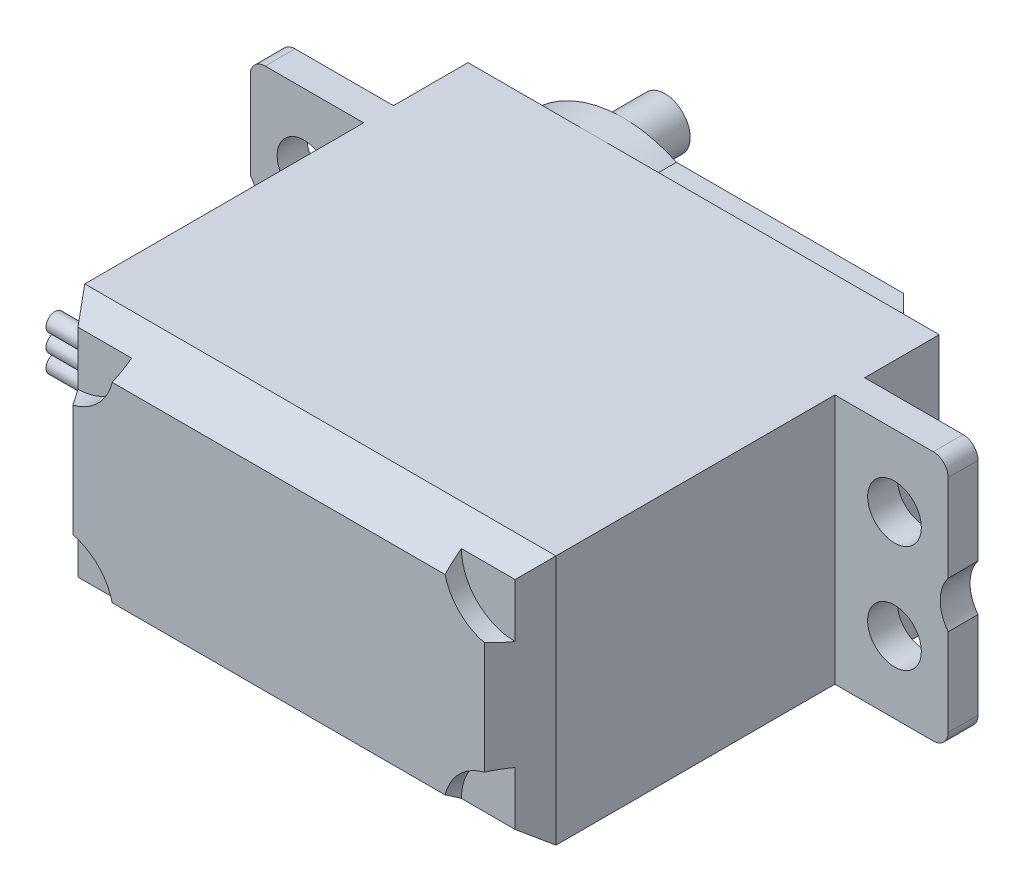
SolidWorks part; units mm, degrees
ref_plane "Front Plane" through (0, 0, 0) normal (0, 0, 1) x (1, 0, 0)
ref_plane "Top Plane" through (0, 0, 0) normal (0, 1, 0) x (1, 0, 0)
ref_plane "Right Plane" through (0, 0, 0) normal (1, 0, 0) x (0, 0, -1)
sketch "Sketch1" plane through (0, 0, 0) normal (0, 0, 1) x (1, 0, 0)
  line L1 (-22.8104, 16.0029) -> (17.3216, 16.0029)
  line L2 (-22.8104, 16.0029) -> (-22.8104, -5.3331)
  line L3 (-22.8104, -5.3331) -> (17.3216, -5.3331)
  line L4 (17.3216, 16.0029) -> (17.3216, -5.3331)
  dimension "D1" = 40.132
  dimension "D2" = 21.336
extrude "Boss-Extrude1" add sketch "Sketch1" along normal blind 36.195
sketch "Sketch5" plane through (0, -5.3331, 0) normal (0, -1, 0) x (1, 0, 0)
  line L0 (-22.8104, 36.195) -> (17.3216, 36.195) construction
  line L1 (-22.8104, 36.195) -> (-22.8104, 0) construction
  line L2 (-22.8104, 0) -> (17.3216, 0) construction
  line L3 (17.3216, 36.195) -> (17.3216, 0) construction
  line L4 (-22.8104, 36.195) -> (17.3216, 36.195)
  line L5 (-22.8104, 36.195) -> (-22.8104, 0)
  line L6 (-22.8104, 0) -> (17.3216, 0)
  line L7 (17.3216, 36.195) -> (17.3216, 0)
sketch "Sketch6" plane through (0, 0, 0) normal (0, 0, -1) x (-1, 0, 0)
  line L0 (22.8104, 16.0029) -> (22.8104, -5.3331) construction
  line L1 (7.5987, 14.9869) -> (-14.2736, 14.9869)
  line L2 (22.8104, -5.3331) -> (-17.3216, -5.3331) construction
  line L3 (-17.3216, 16.0029) -> (22.8104, 16.0029) construction
  line L4 (-14.2736, 14.9869) -> (-14.2736, -4.3171)
  line L5 (-14.2736, -4.3171) -> (7.5987, -4.3171)
  line L6 (22.8104, -5.3331) -> (-17.3216, -5.3331) construction
  line L7 (-17.3216, -5.3331) -> (-17.3216, 16.0029) construction
  circle A0 centre (12.1424, 5.3349) radius 10.668 construction
  arc A1 (7.5987, -4.3171) -> (7.5987, 14.9869) centre (12.1424, 5.3349) ccw
  point P6 (22.8104, 5.3349)
  dimension "D1" = 1.016
  dimension "D2" = 1.016
  dimension "D3" = 3.048
extrude "Boss-Extrude3" add sketch "Sketch6" along normal blind 2.54
chamfer "Chamfer1" distance 2.54 distance2 2.54 1 edges at (14.2736, 5.3349, -2.54)
ref_plane "Plane1" through (0, 0, 8.89) normal (0, 0, -1) x (-1, 0, 0)
sketch "Sketch7" plane through (0, 0, 8.89) normal (0, 0, -1) x (-1, 0, 0)
  line L0 (22.8104, 16.0029) -> (22.8104, -5.3331) construction
  line L1 (22.8104, 16.0029) -> (22.8104, -5.3331)
  line L2 (22.8104, -5.3331) -> (31.1924, -5.3331)
  line L3 (32.4624, -4.0631) -> (32.4624, 3.3593)
  line L4 (31.1924, 16.0029) -> (22.8104, 16.0029)
  line L5 (32.4624, 5.3349) -> (22.8104, 5.3349) construction
  line L6 (32.4624, 5.3349) -> (35.0024, 5.3349) construction
  line L7 (32.4624, 7.3105) -> (32.4624, 14.7329)
  circle A0 centre (27.8904, 0.7629) radius 2.286
  circle A1 centre (27.8904, 9.9069) radius 2.286
  arc A2 (32.4624, 3.3593) -> (32.4624, 7.3105) centre (35.0024, 5.3349) cw
  arc A3 (32.4624, 14.7329) -> (31.1924, 16.0029) centre (31.1924, 14.7329) ccw
  arc A4 (31.1924, -5.3331) -> (32.4624, -4.0631) centre (31.1924, -4.0631) ccw
  point P17 (32.4624, -5.3331)
  dimension "D2" = 4.572
  dimension "D3" = 4.572
  dimension "D9" = 2.54
  dimension "D10" = 1.27
  dimension "D1" = 9.652
  dimension "D4" = 4.572
  dimension "D5" = 5.08
  dimension "D6" = 5.08
  dimension "D7" = 9.144
  dimension "D8" = 3.9511
extrude "Boss-Extrude4" add sketch "Sketch7" along normal blind 2.54
ref_plane "Plane2" through (-2.7444, 0, 0) normal (1, 0, 0) x (0, 0, -1)
mirror "Mirror1" about plane through (-2.7444, 0, 0) normal (1, 0, 0) of "Boss-Extrude4"
chamfer "Chamfer2" distance 3.556 distance2 2.54 4 edges at (17.3216, 5.3349, 36.195) (-2.7444, 16.0029, 36.195) (-2.7444, -5.3331, 36.195) (-22.8104, 5.3349, 36.195) first distance on face at (17.3216, 8.0019, 29.3687) first distance on face at (-2.8225, 16.0029, 11.5521) first distance on face at (-4.1121, -5.3331, 11.5521) first distance on face at (-22.8104, 5.3349, 22.5425)
ref_plane "Plane3" through (0, 0, 34.671) normal (0, 0, 1) x (1, 0, 0)
sketch "Sketch12" plane through (0, 0, 34.671) normal (0, 0, 1) x (1, 0, 0)
  line L0 (-21.3589, 14.5515) -> (-21.3589, -3.8817)
  line L1 (-21.3589, 14.5515) -> (-21.3589, 9.9795)
  line L2 (15.8702, 14.5515) -> (-21.3589, 14.5515)
  line L3 (15.8702, 14.5515) -> (11.2982, 14.5515)
  line L4 (15.8702, -3.8817) -> (15.8702, 14.5515)
  line L5 (15.8702, -3.8817) -> (15.8702, 0.6903)
  line L6 (-21.3589, -3.8817) -> (15.8702, -3.8817)
  line L7 (-21.3589, -3.8817) -> (-16.7869, -3.8817)
  line L8 (-2.7444, 14.9143) -> (-2.7444, -4.2445) construction
  line L9 (-21.7218, 5.3349) -> (16.2331, 5.3349) construction
  line L10 (-21.3589, 0.6903) -> (-21.3589, -3.8817)
  line L11 (11.2982, -3.8817) -> (15.8702, -3.8817)
  line L12 (-16.7869, 14.5515) -> (-21.3589, 14.5515)
  line L13 (15.8702, 9.9795) -> (15.8702, 14.5515)
  arc A0 (-21.3589, 9.9795) -> (-16.7869, 14.5515) centre (-21.3589, 14.5515) ccw
  arc A1 (-21.3589, 0.6903) -> (-16.7869, -3.8817) centre (-21.3589, -3.8817) cw
  arc A2 (15.8702, 0.6903) -> (11.2982, -3.8817) centre (15.8702, -3.8817) ccw
  arc A3 (15.8702, 9.9795) -> (11.2982, 14.5515) centre (15.8702, 14.5515) cw
  dimension "D1" = 4.572
extrude "Cut-Extrude11" cut sketch "Sketch12" along normal up to next
sketch "Sketch13" plane through (0, 0, -2.54) normal (0, 0, -1) x (-1, 0, 0)
  line L1 (20.6514, 7.4939) -> (18.1141, 7.4939)
  line L2 (20.6514, 3.1759) -> (18.1141, 3.1759)
  line L3 (14.3014, -3.1741) -> (14.3014, -0.6368)
  line L4 (9.9834, -3.1741) -> (9.9834, -0.6368)
  line L5 (3.6334, 3.1759) -> (6.1707, 3.1759)
  line L6 (3.6334, 7.4939) -> (6.1707, 7.4939)
  line L7 (9.9834, 13.8439) -> (9.9834, 11.3066)
  line L8 (14.3014, 13.8439) -> (14.3014, 11.3066)
  arc A0 (18.1141, 7.4939) -> (14.3014, 11.3066) centre (12.1424, 5.3349) ccw
  arc A1 (7.5987, -4.3171) -> (7.5987, 14.9869) centre (12.1424, 5.3349) ccw construction
  arc A2 (20.6514, 3.1759) -> (20.6514, 7.4939) centre (20.6514, 5.3349) ccw
  arc A3 (9.9834, -3.1741) -> (14.3014, -3.1741) centre (12.1424, -3.1741) ccw
  arc A4 (3.6334, 7.4939) -> (3.6334, 3.1759) centre (3.6334, 5.3349) ccw
  arc A5 (14.3014, 13.8439) -> (9.9834, 13.8439) centre (12.1424, 13.8439) ccw
  arc A6 (9.9834, 11.3066) -> (6.1707, 7.4939) centre (12.1424, 5.3349) ccw
  arc A7 (6.1707, 3.1759) -> (9.9834, -0.6368) centre (12.1424, 5.3349) ccw
  arc A8 (14.3014, -0.6368) -> (18.1141, 3.1759) centre (12.1424, 5.3349) ccw
  point P27 (12.1424, 5.3349)
  dimension "D1" = 12.7
  dimension "D2" = 4
extrude "Boss-Extrude5" add sketch "Sketch13" along normal blind 1.524
sketch "Sketch14" plane through (0, 0, -4.064) normal (0, 0, -1) x (-1, 0, 0)
  circle A0 centre (12.1424, 13.8439) radius 2.159
  arc A1 (14.3014, 13.8439) -> (9.9834, 13.8439) centre (12.1424, 13.8439) ccw construction
  circle A2 centre (12.1424, 13.8439) radius 1.016
  arc A3 (18.1141, 7.4939) -> (14.3014, 11.3066) centre (12.1424, 5.3349) ccw construction
  arc A4 (18.1141, 7.4939) -> (14.3014, 11.3066) centre (12.1424, 5.3349) ccw construction
  circle A5 centre (20.6514, 5.3349) radius 2.159
  circle A6 centre (20.6514, 5.3349) radius 1.016
  circle A7 centre (12.1424, -3.1741) radius 2.159
  circle A8 centre (12.1424, -3.1741) radius 1.016
  circle A9 centre (3.6334, 5.3349) radius 2.159
  circle A10 centre (3.6334, 5.3349) radius 1.016
  point P21 (12.1424, 5.3349)
  dimension "D1" = 2.032
  dimension "D2" = 4
extrude "Boss-Extrude6" add sketch "Sketch14" along normal blind 2.032
sketch "Sketch15" plane through (0, 0, -4.064) normal (0, 0, -1) x (-1, 0, 0)
  arc A0 (18.1141, 7.4939) -> (14.3014, 11.3066) centre (12.1424, 5.3349) ccw construction
  arc A1 (18.1141, 7.4939) -> (14.3014, 11.3066) centre (12.1424, 5.3349) ccw construction
  circle A2 centre (12.1424, 5.3349) radius 1.27
  circle A3 centre (12.1424, 5.3349) radius 3.048
  dimension "D1" = 2.54
  dimension "D2" = 6.096
extrude "Boss-Extrude7" add sketch "Sketch15" along normal blind 3.556
sketch "Sketch16" plane through (-22.8104, 0, 0) normal (-1, 0, 0) x (0, 0, 1)
  line L0 (32.639, 5.3349) -> (8.89, 5.3349) construction
  line L1 (32.639, -5.3331) -> (32.639, 16.0029) construction
  line L2 (8.89, 5.8674) -> (8.89, -5.8674) construction
  line L3 (27.813, 4.6165) -> (27.813, 4.5293)
  line L4 (27.305, 4.6165) -> (27.305, 4.5293)
  line L5 (27.305, 6.1405) -> (27.305, 6.0533)
  line L7 (27.813, 6.1405) -> (27.813, 6.0533)
  arc A0 (27.305, 6.0533) -> (27.305, 4.6165) centre (27.559, 5.3349) ccw
  arc A1 (27.813, 6.1405) -> (27.305, 6.1405) centre (27.559, 6.8589) ccw
  arc A2 (27.305, 4.5293) -> (27.813, 4.5293) centre (27.559, 3.8109) ccw
  arc A3 (27.813, 4.6165) -> (27.813, 6.0533) centre (27.559, 5.3349) ccw
  dimension "D1" = 1.524
  dimension "D2" = 5.08
  dimension "D3" = 0.254
  dimension "D4" = 0.254
extrude "Boss-Extrude8" add sketch "Sketch16" along normal blind 7.62
